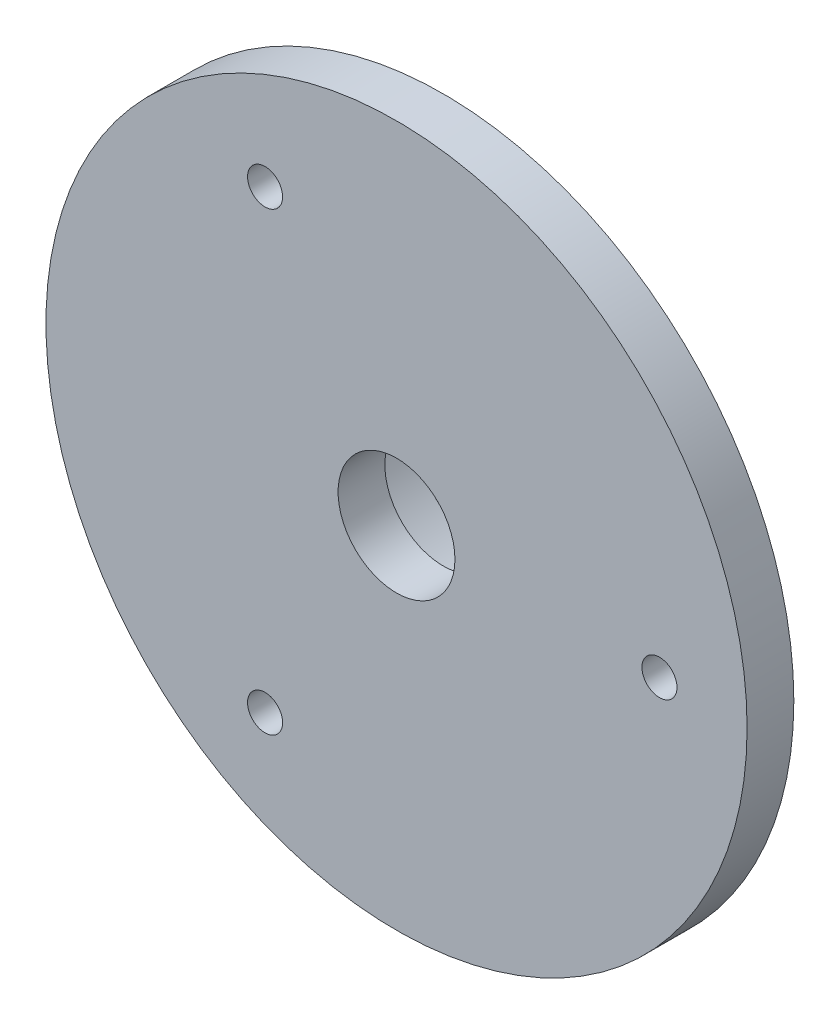
SolidWorks part; units mm, degrees
ref_plane "Front Plane" through (0, 0, 0) normal (0, 0, 1) x (1, 0, 0)
ref_plane "Top Plane" through (0, 0, 0) normal (0, 1, 0) x (1, 0, 0)
ref_plane "Right Plane" through (0, 0, 0) normal (1, 0, 0) x (0, 0, -1)
sketch "Sketch1" plane through (0, 0, 0) normal (0, 0, 1) x (1, 0, 0)
  line L0 (0, 0) -> (125, 0) construction
  line L25 (125, 0) -> (127.5, 0) construction
  line L27 (0, 0) -> (0, -15) construction
  circle A0 centre (0, 0) radius 30
  circle A3 centre (0, 0) radius 5
  circle A26 centre (0, 0) radius 10 construction
  circle A27 centre (0, 0) radius 22.5 construction
  circle A38 centre (22.5, 0) radius 1.5
  circle A39 centre (-11.25, -19.4856) radius 1.5
  circle A40 centre (-11.25, 19.4856) radius 1.5
  point P11 (0, 0)
  point P14 (0, 0)
  point P22 (0, 0)
  point P46 (0, 77.5)
  point P53 (54.8008, 54.8008)
  point P65 (0, 0)
  point P78 (0, 0)
  point P84 (0, 0)
  point P86 (0, 0)
  point P87 (-54.8008, 54.8008)
  dimension "D1" = 60
  dimension "D2" = 3
  dimension "D3" = 20
  dimension "D4" = 10
  dimension "D5" = 3
  dimension "D9" = 45
extrude "Boss-Extrude1" add sketch "Sketch1" along normal blind 4
sketch "Sketch2" plane through (0, 0, 0) normal (0, 0, -1) x (-1, 0, 0)
  circle A1 centre (0, 0) radius 16
  circle A10 centre (0, 0) radius 5 construction
  circle A11 centre (0, 0) radius 5 construction
  circle A12 centre (0, 0) radius 12
  dimension "D1" = 32
  dimension "D2" = 24
extrude "Boss-Extrude2" add sketch "Sketch2" along normal blind 8
